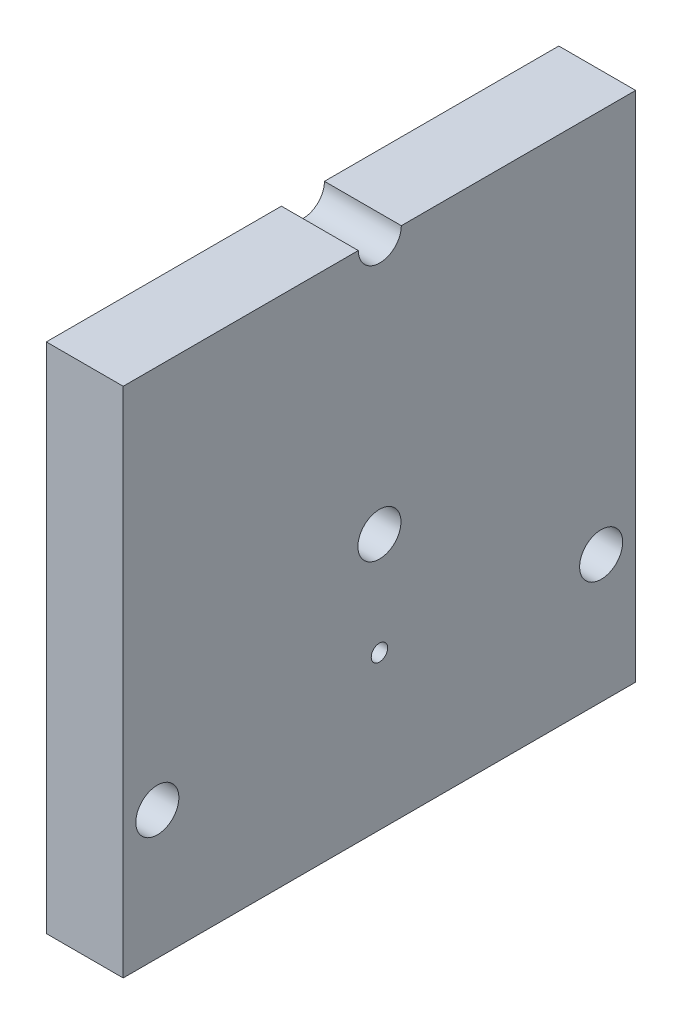
SolidWorks part; units mm, degrees
material "Tungsten"
ref_plane "Ebene vorne" through (0, 0, 0) normal (0, 0, 1) x (1, 0, 0)
ref_plane "Ebene oben" through (0, 0, 0) normal (0, 1, 0) x (1, 0, 0)
ref_plane "Ebene rechts" through (0, 0, 0) normal (1, 0, 0) x (0, 0, -1)
sketch "Sketch2" plane through (0, 0, 0) normal (1, 0, 0) x (0, 0, -1)
  line L0 (0, 50) -> (0, -50) construction
  line L1 (-50, 50) -> (50, 50)
  line L2 (-50, 50) -> (-50, -50)
  line L3 (-50, -50) -> (50, -50)
  line L4 (50, 50) -> (50, -50)
  line L5 (-50, 0) -> (50, 0) construction
  line L7 (-50, 50) -> (50, -50) construction
  circle A0 centre (0, 0) radius 4.2
  point P19 (0, 0)
  point P20 (0, 0)
  point P21 (0, 0)
  dimension "D3" = 8.4
  dimension "D1" = 100
  dimension "D2" = 100
extrude "Boss-Extrude1" add sketch "Sketch2" along normal blind 15
sketch "Sketch3" plane through (0, 0, 0) normal (-1, 0, 0) x (0, 0, 1)
  circle A0 centre (43.337, -24.9381) radius 4.2
  circle A1 centre (-43.2655, -25.0619) radius 4.2
  circle A2 centre (-0.0715, 49.9999) radius 4.2
  point P9 (0, 0)
  dimension "D1" = 8.4
  dimension "D2" = 50
  dimension "D3" = 3
extrude "Cut-Extrude1" cut sketch "Sketch3" against normal through all
sketch "Sketch4" plane through (0, 0, 0) normal (-1, 0, 0) x (0, 0, 1)
  circle A0 centre (0, -20) radius 1.6
  dimension "D1" = 3.2
  dimension "D2" = 20
extrude "Cut-Extrude2" cut sketch "Sketch4" against normal through all
